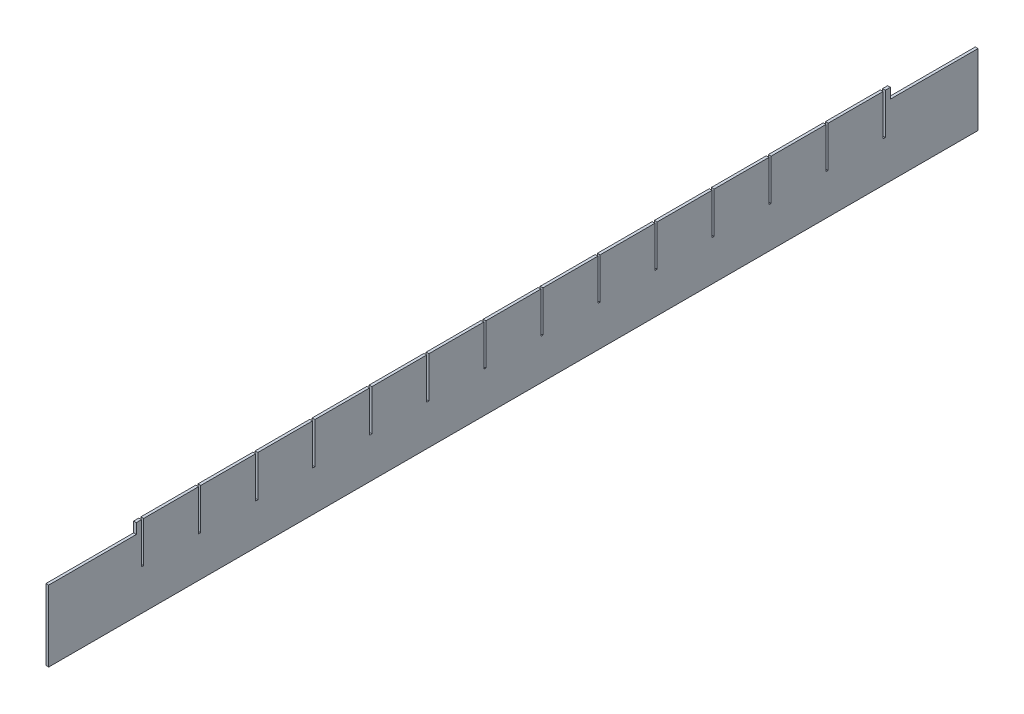
SolidWorks part; units mm, degrees
ref_plane "Front Plane" through (0, 0, 0) normal (0, 0, 1) x (1, 0, 0)
ref_plane "Top Plane" through (0, 0, 0) normal (0, 1, 0) x (1, 0, 0)
ref_plane "Right Plane" through (0, 0, 0) normal (1, 0, 0) x (0, 0, -1)
sketch "MiddlePart" plane through (0, 0, 0) normal (1, 0, 0) x (0, 0, -1)
  line L0 (-33.3333, 23.59) -> (-33.3333, 0)
  line L1 (-33.3333, 0) -> (0, 0)
  line L2 (0, 0) -> (0, 23.59)
  line L3 (-0.64, 47.5) -> (-32.6933, 47.5)
  line L7 (-33.3333, 23.59) -> (-32.6933, 23.59)
  line L8 (-32.6933, 47.5) -> (-32.6933, 23.59)
  line L11 (0, 23.59) -> (-0.64, 23.59)
  line L12 (-0.64, 47.5) -> (-0.64, 23.59)
  dimension "D1" = 33.3333
  dimension "DemiFente" = 0.64
  dimension "D3" = 23.91
  dimension "D5" = 47.5
sketch "FirstPart" plane through (0, 0, 0) normal (1, 0, 0) x (0, 0, -1)
  line L0 (0, 23.59) -> (0, 0)
  line L2 (3.64, 41.5) -> (3.64, 47.5)
  line L3 (3.64, 47.5) -> (0.64, 47.5)
  line L5 (0, 23.59) -> (0.64, 23.59)
  line L7 (0, 23.59) -> (-0.64, 23.59) construction
  line L8 (0.64, 23.59) -> (0.64, 47.5)
  line L9 (-0.64, 47.5) -> (-32.6933, 47.5) construction
  line L11 (3.64, 41.5) -> (54.8333, 41.5)
  line L13 (0, 0) -> (54.8333, 0)
  line L14 (54.8333, 41.5) -> (54.8333, 0)
  dimension "D2" = 6
  dimension "D3" = 54.8333
extrude "Middle" add sketch "MiddlePart" along normal blind 0.8 and the other way blind 0.8
pattern_linear "LPattern3" count 13 spacing 33.3333 along (0, 0, 1) of "Middle"
extrude "First" add sketch "FirstPart" along normal blind 0.8 and the other way blind 0.8
sketch "LastPart" plane through (0, 0, 0) normal (1, 0, 0) x (0, 0, -1)
  line L0 (0, 23.59) -> (0.64, 23.59) construction
  line L1 (-436.9733, 47.5) -> (-433.9733, 47.5)
  line L2 (-436.9733, 47.5) -> (-436.9733, 41.5)
  line L3 (-488.1667, 0) -> (-433.3333, 0)
  line L4 (-433.3333, 23.59) -> (-433.3333, 0)
  line L5 (3.64, 47.5) -> (0.64, 47.5) construction
  line L7 (-433.3333, 23.59) -> (-433.9733, 23.59)
  line L8 (-433.9733, 47.5) -> (-433.9733, 23.59)
  line L9 (3.64, 41.5) -> (3.64, 47.5) construction
  line L10 (0, 0) -> (54.8333, 0) construction
  line L12 (54.8333, 41.5) -> (3.64, 41.5) construction
  line L13 (-436.9733, 41.5) -> (-488.1667, 41.5)
  line L14 (-488.1667, 0) -> (-488.1667, 41.5)
  line L15 (54.8333, 0) -> (54.8333, 41.5) construction
  dimension "D1" = 543
extrude "Last" add sketch "LastPart" along normal blind 0.8 and the other way blind 0.8
equation "\"Coté\"= 33.333333"
equation "\"nbCarre\"= 13"
equation "\"jeu\"= 0.16"
equation "\"epaisseur\"= 1.6"
equation "\"hauteur\"= 47.5"
equation "\"rapportEncoche\"= 0.5"
equation "\"D1@MiddlePart\"= \"Coté\""
equation "\"DemiFente@MiddlePart\"= \"epaisseur\" / 2 - \"jeu\""
equation "\"D3@MiddlePart\"      = \"hauteur\" * ( 1 - \"rapportEncoche\" ) + \"jeu\""
equation "\"D5@MiddlePart\"= \"hauteur\""
equation "\"D1@Middle\"=\"epaisseur\"/2"
equation "\"D3@LPattern3\"=\"Coté\""
equation "\"D1@LPattern3\"=\"nbCarre\""
equation "\"D1@First\"=\"epaisseur\"/2"
equation "\"D1@Last\"=\"epaisseur\"/2"
equation "\"D2@Middle\"=\"epaisseur\"/2"
equation "\"D2@First\"=\"epaisseur\"/2"
equation "\"D2@Last\"= \"epaisseur\" / 2"
equation "\"CotéTable\"= 543"
equation "\"D1@LastPart\" = \"CotéTable\""
equation "\"D3@FirstPart\"   = ( \"CotéTable\" - \"nbCarre\" * \"Coté\" ) / 2"
